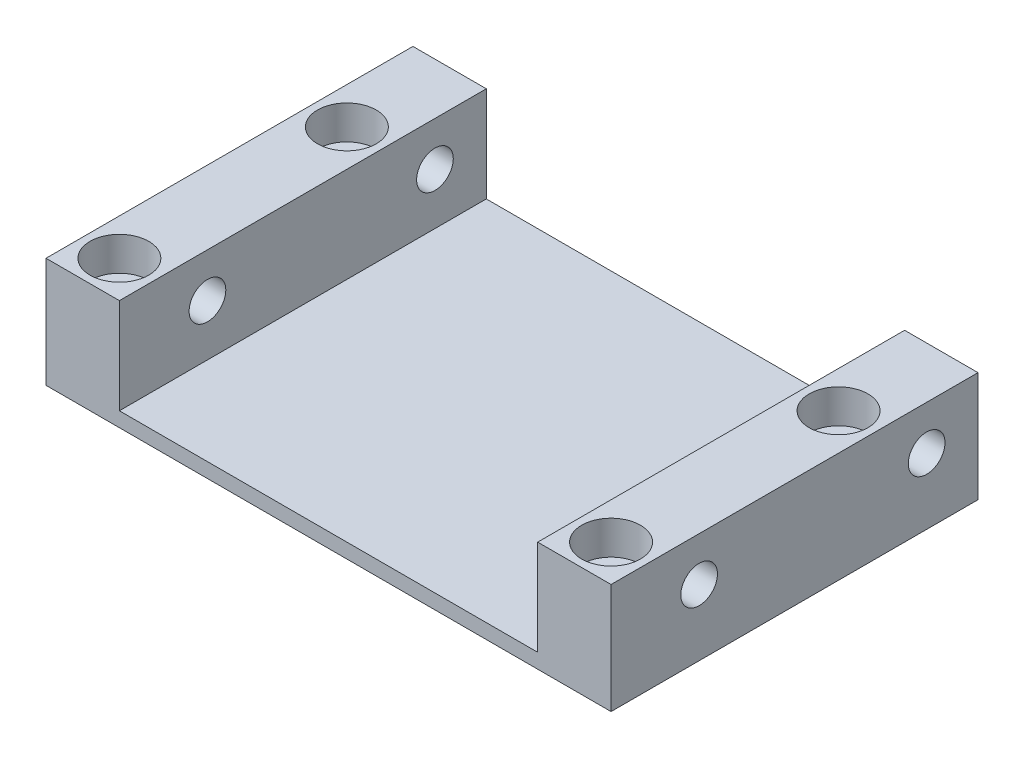
SolidWorks part; units mm, degrees
material "1060 合金"
ref_plane "前视基准面" through (0, 0, 0) normal (0, 0, 1) x (1, 0, 0)
ref_plane "上视基准面" through (0, 0, 0) normal (0, 1, 0) x (1, 0, 0)
ref_plane "右视基准面" through (0, 0, 0) normal (1, 0, 0) x (0, 0, -1)
sketch "草图1" plane through (0, 0, 0) normal (0, 0, 1) x (1, 0, 0)
  line L0 (0, 0) -> (0, 27.6431) construction
  line L3 (-28.5, 2) -> (-28.5, 15)
  line L4 (-28.5, 15) -> (-38.5, 15)
  line L5 (-38.5, 15) -> (-38.5, 0)
  line L10 (38.5, 15) -> (38.5, 0)
  line L11 (28.5, 15) -> (38.5, 15)
  line L12 (28.5, 2) -> (28.5, 15)
  line L13 (-28.5, 2) -> (28.5, 2)
  line L14 (38.5, 0) -> (-38.5, 0)
  dimension "D1" = 57
  dimension "D2" = 2
  dimension "D3" = 13
  dimension "D6" = 10
extrude "凸台-拉伸1" add sketch "草图1" against normal mid plane 50
sketch "草图4" plane through (0, 0, 0) normal (1, 0, 0) x (0, 0, -1)
  line L1 (25, 0) -> (25, 15) construction
  line L2 (25, 15) -> (-25, 15) construction
  circle A0 centre (18, 9) radius 2.5
  circle A2 centre (18, 9) radius 2.5 construction
  circle A4 centre (-13, 9) radius 2.5 construction
  circle A5 centre (-13, 9) radius 2.5
  dimension "D3" = 5
  dimension "D1" = 6
  dimension "D2" = 31
  dimension "D4" = 7
extrude "切除-拉伸1" cut sketch "草图4" against normal mid plane 100
hole_wizard "打孔尺寸根据内六角圆柱头螺钉的类型2" positions "草图10" profile "草图9" counterbore size "M4" standard "GB" end condition through all
sketch "草图10" plane through (0, 15, 0) normal (0, 1, 0) x (-1, 0, 0)
  line L0 (38.5, 13) -> (28.5, 13) construction
  line L1 (38.5, -18) -> (28.5, -18) construction
  line L2 (38.5, -25) -> (38.5, 25) construction
  point P0 (33.5, -11)
  point P1 (33.5, 20)
  dimension "D1" = 7
  dimension "D2" = 7
  dimension "D3" = 5
sketch "草图9" plane through (-33.5, 15, -11) normal (1, 0, 0) x (0, 0, 1)
  line L0 (0, 0) -> (0, 15)
  line L1 (0, 15) -> (2.25, 15)
  line L3 (2.25, 15) -> (2.25, 4.6)
  line L4 (2.25, 4.6) -> (4, 4.6)
  line L5 (4, 4.6) -> (4, 0)
  line L7 (4, 0) -> (0, 0)
  line L11 (0, -6.35) -> (0, 107.95) construction
  dimension "通孔孔直径" = 4.5
  dimension "通孔孔深度" = 15
  dimension "柱形沉头孔直径" = 8
  dimension "柱形沉头孔深度" = 4.6
mirror "镜向2" about plane through (0, 0, 0) normal (1, 0, 0) of "打孔尺寸根据内六角圆柱头螺钉的类型2"
